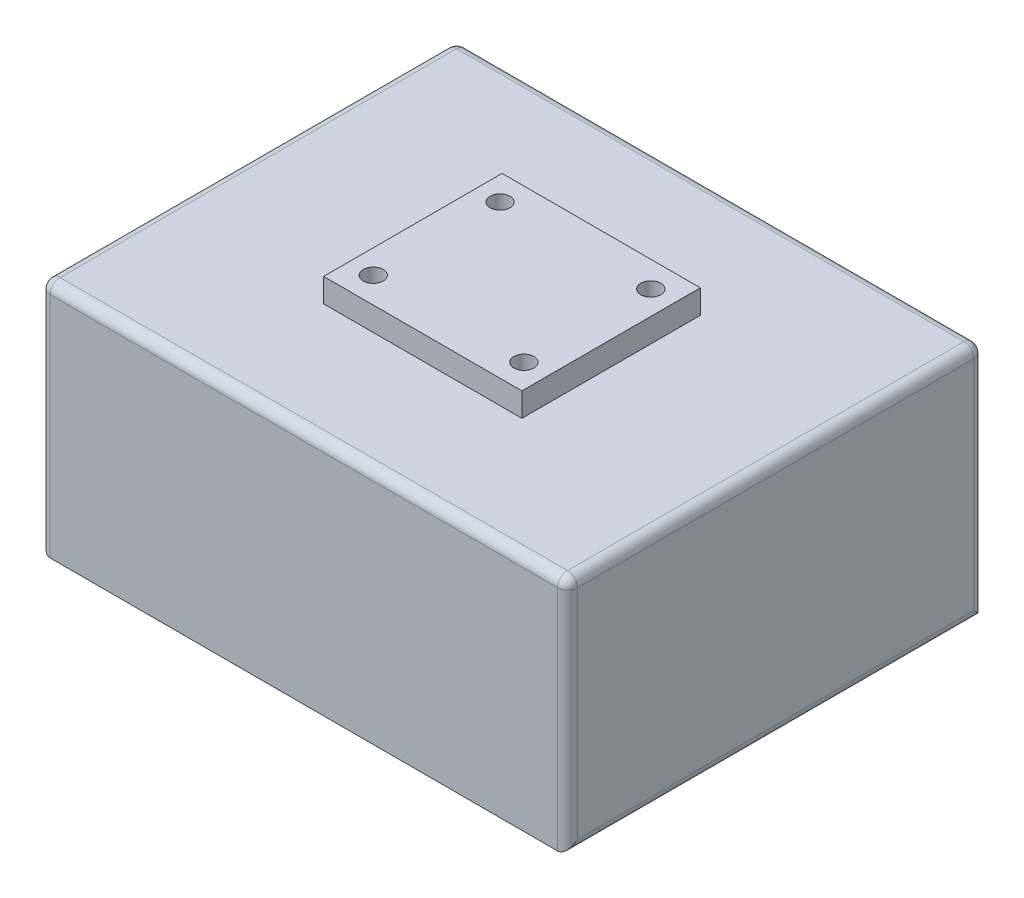
SolidWorks part; units mm, degrees
ref_plane "Front Plane" through (0, 0, 0) normal (0, 0, 1) x (1, 0, 0)
ref_plane "Top Plane" through (0, 0, 0) normal (0, 1, 0) x (1, 0, 0)
ref_plane "Right Plane" through (0, 0, 0) normal (1, 0, 0) x (0, 0, -1)
sketch "Sketch1" plane through (0, 0, 0) normal (0, 1, 0) x (1, 0, 0)
  line L1 (0, 0) -> (133, 0)
  line L2 (0, 0) -> (0, 105)
  line L3 (0, 105) -> (133, 105)
  line L4 (133, 0) -> (133, 105)
  dimension "D1" = 105
  dimension "D2" = 133
extrude "Boss-Extrude1" add sketch "Sketch1" along normal blind 60
sketch "Sketch2" plane through (0, 0, 0) normal (-1, 0, 0) x (0, 0, 1)
  line L0 (-105, 0) -> (0, 0) construction
  line L1 (-99, 0) -> (-6, 0)
  arc A0 (-6, 0) -> (-99, 0) centre (-52.5, 0) ccw
  dimension "D1" = 93
extrude "Cut-Extrude1" cut sketch "Sketch2" against normal offset from surface (129 mm away) 2 from offset 2 up to face at (133, 30, -52.5) offset against normal yes
sketch "Sketch3" plane through (0, 0, 0) normal (-1, 0, 0) x (0, 0, 1)
  line L0 (-105, 0) -> (0, 0) construction
  circle A0 centre (-52.5, 0) radius 42.5
  dimension "D1" = 85
extrude "Cut-Extrude2" cut sketch "Sketch3" against normal blind 10
fillet "Fillet1" radius 2.5 12 edges at (66.5, 60, -105) (133, 60, -52.5) (66.5, 60, 0) (0, 60, -52.5) (133, 30, 0) (133, 30, -105) (133, 0, -52.5) (0, 30, -105) (0, 30, 0) (0, 0, -5) (0, 42.5, -52.5) (0, 0, -100)
sketch "Sketch4" plane through (0, 60, 0) normal (0, 1, 0) x (1, 0, 0)
  line L0 (2.5, 102.5) -> (130.5, 2.5) construction
  line L1 (2.5, 2.5) -> (130.5, 102.5) construction
  line L3 (41.5, 75) -> (91.5, 75)
  line L4 (41.5, 75) -> (41.5, 30)
  line L5 (41.5, 30) -> (91.5, 30)
  line L6 (91.5, 75) -> (91.5, 30)
  line L7 (41.5, 75) -> (91.5, 30) construction
  line L8 (41.5, 30) -> (91.5, 75) construction
  point P8 (66.5, 52.5)
  dimension "D1" = 50
  dimension "D2" = 45
extrude "Boss-Extrude2" add sketch "Sketch4" along normal blind 6
sketch "Sketch5" plane through (0, 66, 0) normal (0, 1, 0) x (1, 0, 0)
  line L0 (41.5, 75) -> (41.5, 30) construction
  line L1 (91.5, 75) -> (41.5, 75) construction
  line L3 (91.5, 30) -> (91.5, 75) construction
  line L5 (41.5, 30) -> (91.5, 30) construction
  circle A0 centre (47.5, 68.5) radius 2.525
  circle A1 centre (85.5, 68.5) radius 2.525
  circle A2 centre (85.5, 36.5) radius 2.525
  circle A3 centre (47.5, 36.5) radius 2.525
  point P10 (41.5, 52.5)
  point P13 (66.5, 75)
  point P16 (91.5, 52.5)
  point P19 (66.5, 30)
  dimension "D1" = 5.05
  dimension "D2" = 5.05
  dimension "D9" = 5.05
  dimension "D10" = 5.05
  dimension "D3" = 16
  dimension "D4" = 19
  dimension "D5" = 19
  dimension "D6" = 16
  dimension "D7" = 16
  dimension "D8" = 19
  dimension "D11" = 19
  dimension "D12" = 16
extrude "Cut-Extrude3" cut sketch "Sketch5" against normal blind 4
sketch "Sketch6" plane through (2, 0, 0) normal (1, 0, 0) x (0, 0, -1)
  line L0 (95, 0.0505) -> (99, 0.0505) construction
  line L1 (95, 0.0505) -> (99, 0.0505)
  line L2 (6, 0.0505) -> (10, 0.0505) construction
  line L3 (6, 0.0505) -> (10, 0.0505)
  arc A0 (95, 0.0505) -> (10, 0.0505) centre (52.5, 0) ccw construction
  arc A1 (95, 0.0505) -> (10, 0.0505) centre (52.5, 0) ccw
  arc A2 (99, 0.0505) -> (6, 0.0505) centre (52.5, 0) ccw construction
  arc A3 (99, 0.0505) -> (6, 0.0505) centre (52.5, 0) ccw
extrude "Boss-Extrude3" add sketch "Sketch6" along normal blind 5 from offset 6.5
sketch "Sketch7" plane through (131, 0, 0) normal (-1, 0, 0) x (0, 0, 1)
  line L0 (-6, 0.0505) -> (-10, 0.0505) construction
  line L1 (-6, 0.0505) -> (-10, 0.0505)
  line L2 (-95, 0.0505) -> (-99, 0.0505) construction
  line L3 (-95, 0.0505) -> (-99, 0.0505)
  arc A0 (-6, 0.0505) -> (-99, 0.0505) centre (-52.5, 0) ccw construction
  arc A1 (-6, 0.0505) -> (-99, 0.0505) centre (-52.5, 0) ccw
  arc A2 (-10, 0.0505) -> (-95, 0.0505) centre (-52.5, 0) ccw construction
  arc A3 (-10, 0.0505) -> (-95, 0.0505) centre (-52.5, 0) ccw
extrude "Boss-Extrude4" add sketch "Sketch7" along normal blind 5 from offset 6.5
ref_plane "Plane1" through (2, 0, 0) normal (-1, 0, 0) x (0, 0, 1)
sketch "Sketch14" plane through (2, 0, 0) normal (-1, 0, 0) x (0, 0, 1)
  line L1 (-28.8158, 40.0163) -> (-22.5318, 44.1104) construction
  line L2 (-12.4837, 23.6842) -> (-8.3896, 29.9682) construction
  line L4 (-52.5, 46.5) -> (-52.5, 0) construction
  line L5 (-52.5, 0) -> (-11.9252, 40.5748) construction
  line L6 (-22.5318, 44.1104) -> (-18.9962, 47.6459)
  line L7 (-18.9962, 47.6459) -> (-4.8541, 33.5038)
  line L8 (-4.8541, 33.5038) -> (-8.3896, 29.9682)
  line L9 (-12.5936, 14.6193) -> (-9.0163, 16.4747)
  line L10 (-52.5, 0) -> (-22.448, 30.052) construction
  line L11 (-37.8807, 39.9064) -> (-36.0253, 43.4837)
  arc A0 (-6, 0) -> (-99, 0) centre (-52.5, 0) ccw construction
  arc A1 (-22.5318, 44.1104) -> (-36.0253, 43.4837) centre (-30.0023, 59.381) cw
  arc A2 (-8.3896, 29.9682) -> (-9.0163, 16.4747) centre (6.881, 22.4977) ccw
  arc A3 (-9.0163, 16.4747) -> (-36.0253, 43.4837) centre (-52.5, 0) ccw construction
  arc A4 (-12.5936, 14.6193) -> (-37.8807, 39.9064) centre (-52.5, 0) ccw
  arc A5 (-10, 0.0505) -> (-95, 0.0505) centre (-52.5, 0) ccw construction
  dimension "D1" = 20
  dimension "D4" = 17
  dimension "D5" = 17
  dimension "D2" = 8
  dimension "D3" = 8
  dimension "D6" = 7.5
  dimension "D7" = 7.5
  dimension "D8" = 45
  dimension "D9" = 5
  dimension "D10" = 57.3815
  dimension "D11" = 45
extrude "Cut-Extrude5" cut sketch "Sketch14" against normal up to surface (129 mm away) up to face at (131, 23.2753, -52.5)
ref_plane "Plane4" through (0, 0, -52.5) normal (0, 0, -1) x (-1, 0, 0)
mirror "Mirror3" about plane through (0, 0, -52.5) normal (0, 0, -1) of "Cut-Extrude5"
ref_plane "Plane5" [suppressed] through (66.5, 0, 0) normal (1, 0, 0) x (0, 0, -1)
mirror "Mirror4" [suppressed] about plane through (66.5, 0, 0) normal (1, 0, 0)
